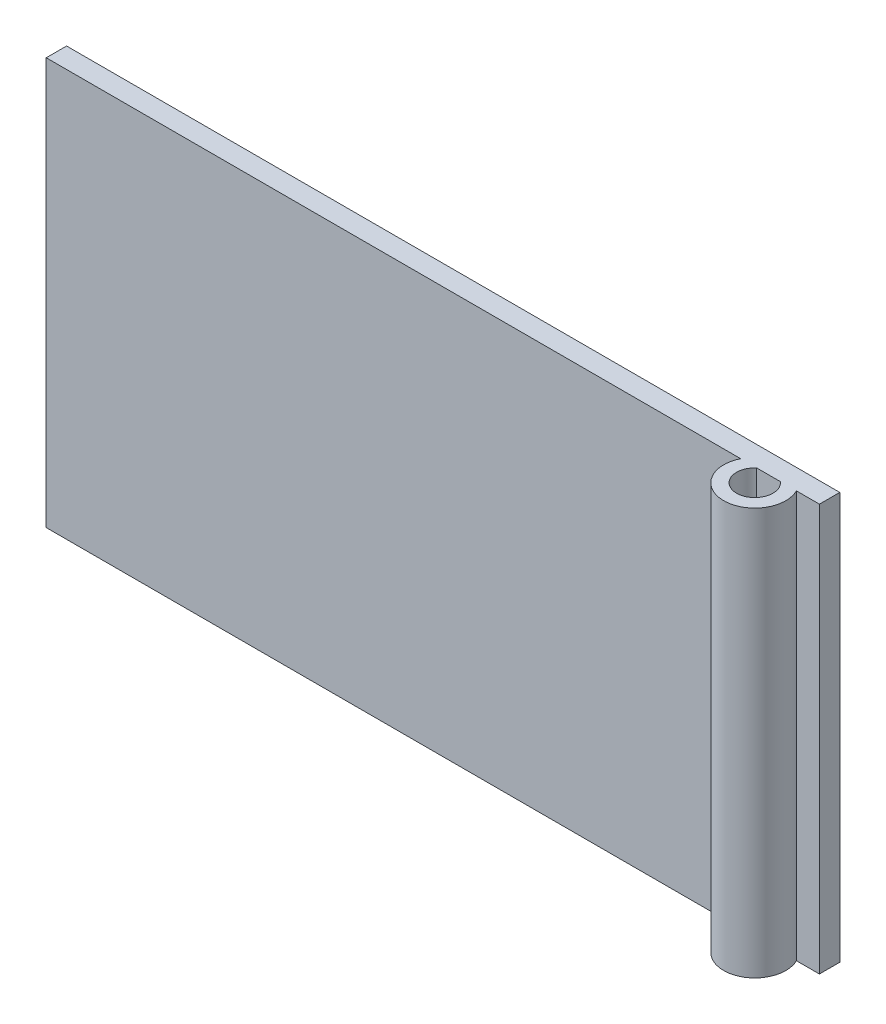
SolidWorks part; units mm, degrees
material "Legs"
ref_plane "Front Plane" through (0, 0, 0) normal (0, 0, 1) x (1, 0, 0)
ref_plane "Top Plane" through (0, 0, 0) normal (0, 1, 0) x (1, 0, 0)
ref_plane "Right Plane" through (0, 0, 0) normal (1, 0, 0) x (0, 0, -1)
sketch "Sketch1" plane through (0, 0, 0) normal (0, 0, 1) x (1, 0, 0)
  line L1 (-190, -100) -> (190, -100)
  line L2 (-190, -100) -> (-190, 100)
  line L3 (-190, 100) -> (190, 100)
  line L4 (190, -100) -> (190, 100)
  line L5 (-190, -100) -> (190, 100) construction
  line L6 (-190, 100) -> (190, -100) construction
  point P0 (0, 0)
  dimension "D1" = 380
  dimension "D2" = 200
extrude "Foot" add sketch "Sketch1" along normal blind 10
sketch "Sketch2" plane through (0, 0, 0) normal (0, 1, 0) x (1, 0, 0)
  circle A0 centre (165.0049, -16.7788) radius 15.2736
  circle A1 centre (165.0049, -16.7788) radius 8.943
extrude "Boss-Extrude2" add sketch "Sketch2" along normal up to surface and the other way up to surface up to face at (0, 100, 5) other way up to face at (0, -100, 5)
